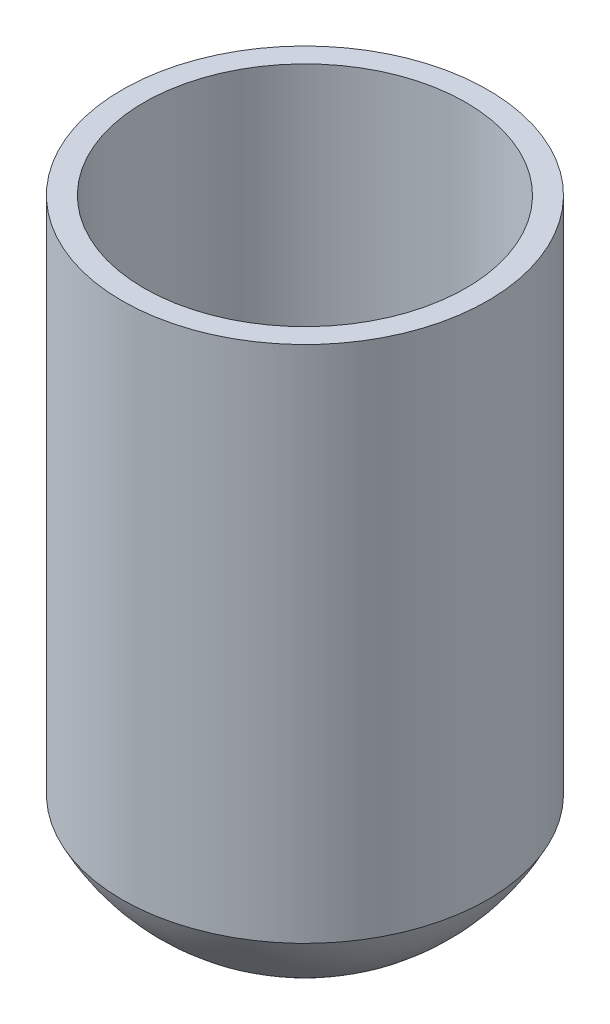
SolidWorks part; units mm, degrees
material "PC High Viscosity"
ref_plane "Front Plane" through (0, 0, 0) normal (0, 0, 1) x (1, 0, 0)
ref_plane "Top Plane" through (0, 0, 0) normal (0, 1, 0) x (1, 0, 0)
ref_plane "Right Plane" through (0, 0, 0) normal (1, 0, 0) x (0, 0, -1)
sketch "Sketch1" plane through (0, 0, 0) normal (0, 1, 0) x (1, 0, 0)
  circle A0 centre (0, 0) radius 28.6537
  circle A1 centre (0, 0) radius 25.2222
  dimension "D1" = 57.3075
  dimension "D2" = 50.4444
extrude "Boss-Extrude1" add sketch "Sketch1" along normal blind 69.85
extrude "Boss-Extrude2" add sketch "Sketch1<3>" against normal blind 11.43 contours A1 | A0 A1 region at (-27.8433, 0, 0) region at (0, 0, 0)
sketch "Sketch1<3>" plane through (0, 0, 0) normal (0, 1, 0) x (1, 0, 0) same geometry as "Sketch1"
dome "Dome1" faces to dome 1 distance 17.78 reverse direction no elliptical dome no face at (0, -11.43, 28.6537) parameters "D1"=17.78
